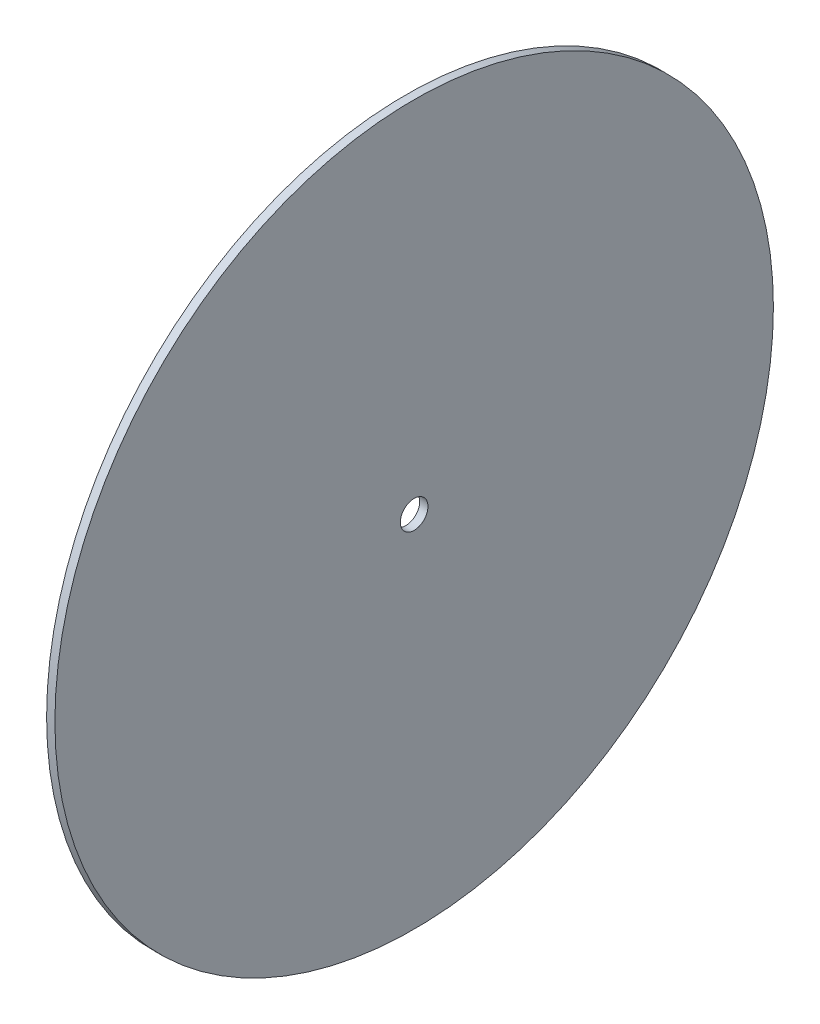
SolidWorks part; units mm, degrees
ref_plane "Front Plane" through (0, 0, 0) normal (0, 0, 1) x (1, 0, 0)
ref_plane "Top Plane" through (0, 0, 0) normal (0, 1, 0) x (1, 0, 0)
ref_plane "Right Plane" through (0, 0, 0) normal (1, 0, 0) x (0, 0, -1)
sketch "Sketch1" plane through (0, 0, 0) normal (1, 0, 0) x (0, 0, -1)
  circle A0 centre (0, 0) radius 130
  circle A1 centre (0, 0) radius 5
  dimension "D1" = 260
  dimension "D2" = 10
extrude "Boss-Extrude1" add sketch "Sketch1" along normal blind 3
